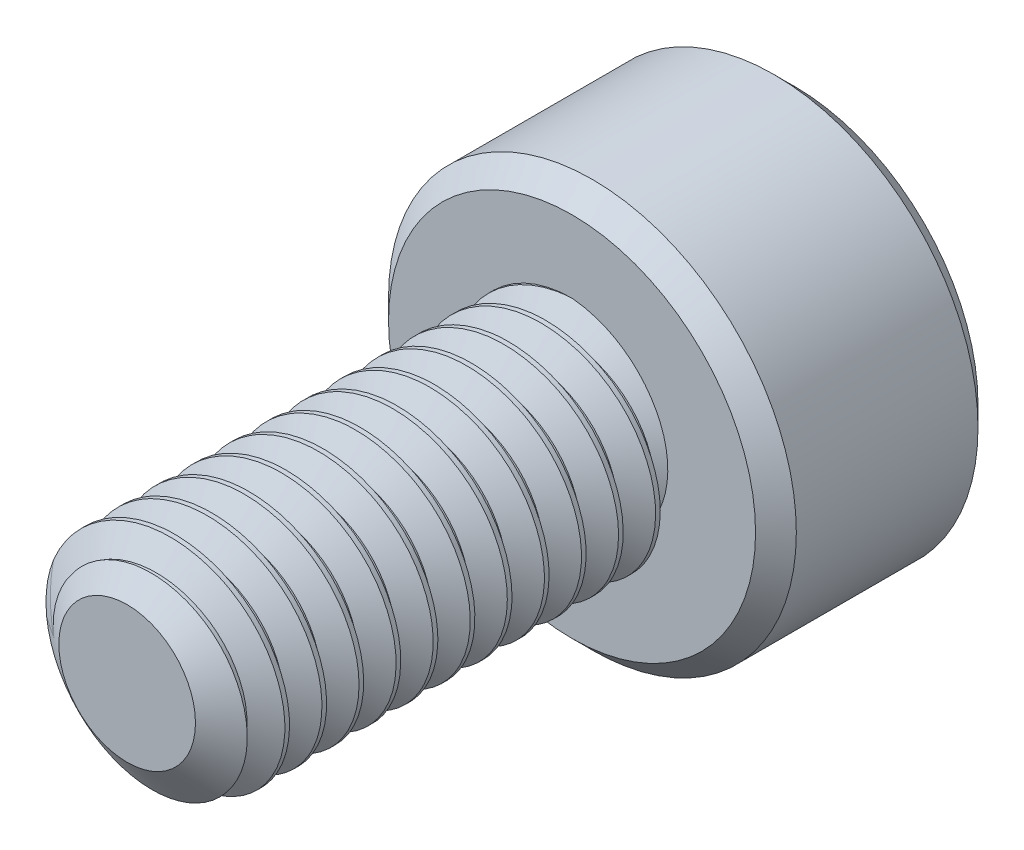
SolidWorks part; units mm, degrees
ref_plane "Front Plane" through (0, 0, 0) normal (0, 0, 1) x (1, 0, 0)
ref_plane "Top Plane" through (0, 0, 0) normal (0, 1, 0) x (1, 0, 0)
ref_plane "Right Plane" through (0, 0, 0) normal (1, 0, 0) x (0, 0, -1)
sketch "Sketch1" plane through (0, 0, 0) normal (0, 0, 1) x (1, 0, 0)
  circle A0 centre (0, 0) radius 1.5
  dimension "OD" = 3
extrude "Extrude1" add sketch "Sketch1" against normal blind 6
sketch "Sketch2" plane through (0, 0, 0) normal (0, 0, 1) x (1, 0, 0)
  circle A0 centre (0, 0) radius 1.5 construction
  circle A1 centre (0, 0) radius 1.5
curve "Helix/Spiral1" pitch 0.5 height 8.5 radius 1.5 centre (0, 0, 0) axis (0, 0, -1) start towards (0, 1, 0) parameters "pitch"=0.5
sketch "Sketch3" plane through (0, 0, 0) normal (1, 0, 0) x (0, 0, -1)
  line L0 (-0.4375, 1.5) -> (-0.25, 1.1752)
  line L1 (-0.25, 1.1752) -> (-0.1875, 1.1752)
  line L2 (-0.1875, 1.1752) -> (0, 1.5)
  line L3 (-0.4375, 1.5) -> (0, 1.5)
  line L4 (-0.2187, 1.5) -> (-0.2188, 1.1752) construction
  line L5 (-0.3438, 1.3376) -> (-0.0938, 1.3376) construction
  line L6 (0, 1.5) -> (0, -1.5) construction
  dimension "D1" = 0.0625
  dimension "D2" = 0.25
  dimension "D3" = 60
sweep "Cut-Sweep1" cut profiles "Sketch3" path "Helix/Spiral1"
sketch "Sketch4" plane through (0, 0, 0) normal (1, 0, 0) x (0, 0, -1)
  line L0 (0.4053, 1.5) -> (0, 0.9212)
  line L1 (0, 0.9212) -> (0, 1.5)
  line L2 (0.4053, 1.5) -> (0, 1.5)
  line L3 (-0.4375, 1.5) -> (0, 1.5) construction
  line L4 (0, 0) -> (7.0209, 0) construction
  dimension "D1" = 55
  dimension "D2" = 0.254
revolve "Cut-Revolve1" cut sketch "Sketch4" angle 360 about L4
sketch "Sketch6" plane through (0, 0, -6) normal (0, 0, -1) x (-1, 0, 0)
  circle A0 centre (0, 0) radius 2.75
  dimension "head dia" = 5.5
extrude "Extrude2" add sketch "Sketch6" along normal blind 3
sketch "Sketch7" plane through (0, 0, -9) normal (0, 0, -1) x (-1, 0, 0)
  line L1 (0, 1.4434) -> (-1.25, 0.7217)
  line L2 (-1.25, 0.7217) -> (-1.25, -0.7217)
  line L3 (-1.25, -0.7217) -> (0, -1.4434)
  line L4 (0, -1.4434) -> (1.25, -0.7217)
  line L5 (1.25, -0.7217) -> (1.25, 0.7217)
  line L6 (1.25, 0.7217) -> (0, 1.4434)
  circle A0 centre (0, 0) radius 1.25 construction
  dimension "hex dia" = 2.5
extrude "Cut-Extrude1" cut sketch "Sketch7" against normal blind 1.875
sketch "Sketch8" plane through (0, 0, -9) normal (0, 0, -1) x (-1, 0, 0)
  circle A0 centre (0, 0) radius 1.4434
extrude "Cut-Extrude2" cut sketch "Sketch8" against normal through all draft 45
chamfer "Chamfer1" distance 0.275 angle 45 2 edges at (-2.75, 0, -9) (-2.75, 0, -6)
sketch "Sketch10" plane through (0, 0, -6) normal (0, 0, 1) x (1, 0, 0)
  circle A1 centre (0, 0) radius 1.5
  circle A2 centre (0, 0) radius 1.5
  dimension "D1" = 0
ref_plane "Plane1" through (0, 0, 0) normal (0, 0, 1) x (1, 0, 0)
extrude "partial thread" [suppressed] add sketch "Sketch10" along normal up to surface (4 mm away) separate body up to plane "Plane1"
chamfer "Chamfer2" [suppressed] distance 0.06 angle 45
combine bodies "Combine1" [suppressed] operation type add bodies to combine 107 108
sketch "Sketch9" plane through (0, 0, 0) normal (1, 0, 0) x (0, 0, -1)
  line L0 (0, 1.5) -> (0, -1.5) construction
  line L1 (1.25, 1.5) -> (1.25, -1.5) construction
  dimension "D1" = 1.25
equation "\"D3@Helix/Spiral1\" = \"screw length@Extrude1\"+\"pitch@Helix/Spiral1\""
equation "\"D1@Sketch3\" = \"pitch@Helix/Spiral1\"*.125"
equation "\"D2@Sketch3\" = \"pitch@Helix/Spiral1\"*.5"
equation "\"D1@Cut-Extrude1\" = \"hex dia@Sketch7\"*.75"
equation "\"D1@Chamfer1\" = \"head dia@Sketch6\"*.05"
equation "\"D1@Sketch9\" = \"pitch@Helix/Spiral1\"*2.5"
equation "\"D1@Chamfer2\"=\"OD@Sketch1\"*.02"
